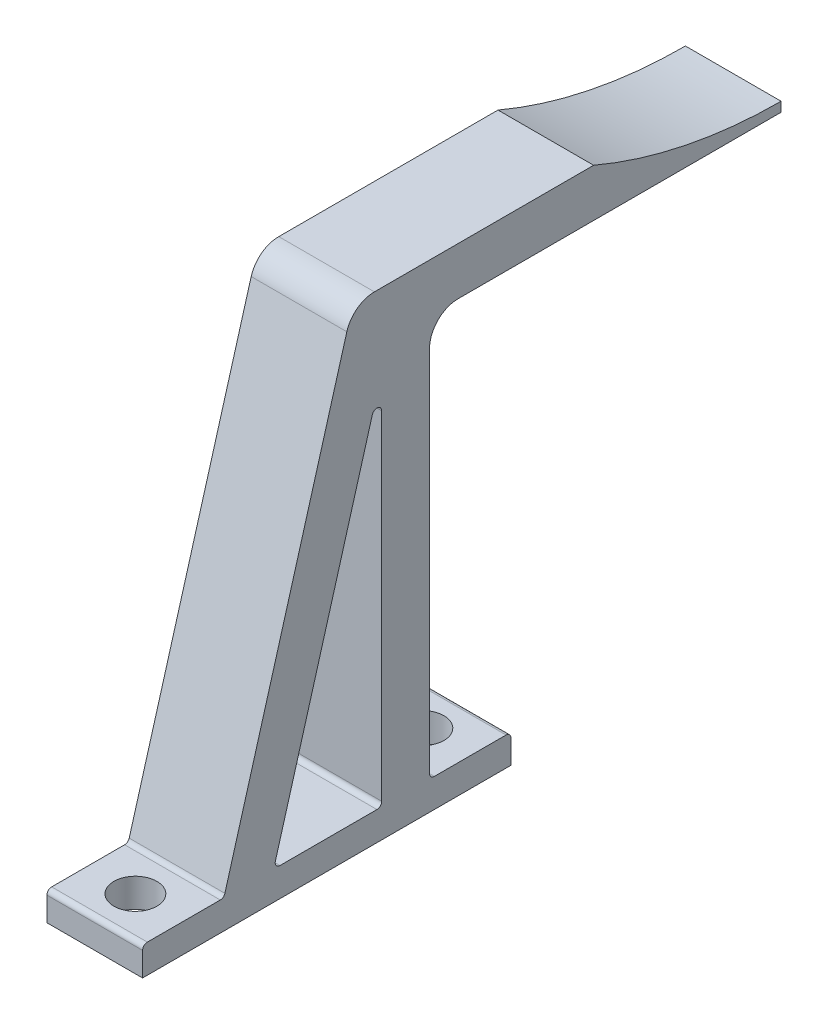
SolidWorks part; units mm, degrees
ref_plane "Front Plane" through (0, 0, 0) normal (0, 0, 1) x (1, 0, 0)
ref_plane "Top Plane" through (0, 0, 0) normal (0, 1, 0) x (1, 0, 0)
ref_plane "Right Plane" through (0, 0, 0) normal (1, 0, 0) x (0, 0, -1)
sketch "Sketch1" plane through (0, 0, 0) normal (1, 0, 0) x (0, 0, -1)
  line L0 (7.9802, 33.6971) -> (-4.7699, -10.7677)
  line L1 (-13.3737, -14.1299) -> (25.1263, -14.1299)
  line L2 (25.1263, -14.1299) -> (25.1263, -11.6299)
  line L3 (24.6263, -11.1299) -> (17.1263, -11.1299)
  line L4 (16.6263, -10.6299) -> (16.6263, 27.8701)
  line L5 (53.3763, 31.8701) -> (53.3763, 30.8701)
  line L6 (10.864, 35.8701) -> (33.7804, 35.8701)
  line L7 (53.3763, 30.8701) -> (19.6263, 30.8701)
  line L8 (-5.2505, -11.1299) -> (-12.8737, -11.1299)
  line L9 (-13.3737, -11.6299) -> (-13.3737, -14.1299)
  line L11 (0.9913, -11.1299) -> (11.1263, -11.1299)
  line L12 (11.6263, -10.6299) -> (11.6263, 24.715)
  line L13 (10.6457, 24.8528) -> (0.5107, -10.492)
  arc A0 (53.3763, 31.8701) -> (33.7804, 35.8701) centre (53.3763, 81.8701) cw
  arc A1 (0.9913, -11.1299) -> (0.5107, -10.492) centre (0.9913, -10.6299) cw
  arc A2 (19.6263, 30.8701) -> (16.6263, 27.8701) centre (19.6263, 27.8701) ccw
  arc A3 (11.6263, 24.715) -> (10.6457, 24.8528) centre (11.1263, 24.715) ccw
  arc A4 (7.9802, 33.6971) -> (10.864, 35.8701) centre (10.864, 32.8701) cw
  arc A5 (-4.7699, -10.7677) -> (-5.2505, -11.1299) centre (-5.2505, -10.6299) cw
  arc A6 (17.1263, -11.1299) -> (16.6263, -10.6299) centre (17.1263, -10.6299) cw
  arc A7 (-12.8737, -11.1299) -> (-13.3737, -11.6299) centre (-12.8737, -11.6299) ccw
  arc A8 (25.1263, -11.6299) -> (24.6263, -11.1299) centre (24.6263, -11.6299) ccw
  arc A9 (11.1263, -11.1299) -> (11.6263, -10.6299) centre (11.1263, -10.6299) ccw
  point P6 (0, 0)
  point P11 (0, 0)
  point P13 (16.4038, 32.062)
  point P14 (0, 0)
  point P22 (0, 0)
  point P26 (-4.8737, -11.1299)
  point P29 (16.6263, -11.1299)
  point P37 (0, 0)
  point P38 (16.2515, 26.3399)
  point P39 (0, 0)
  point P40 (0, 0)
  point P41 (16.9169, 31.2635)
  point P42 (0, 0)
  point P43 (11.1263, 31.1305)
  point P44 (0, 0)
  dimension "D1" = 50
  dimension "D12" = 0.5
  dimension "D14" = 3
  dimension "D16" = 0.5
  dimension "D17" = 0.5
  dimension "D18" = 0.5
  dimension "D19" = 0.5
  dimension "D22" = 0.5
  dimension "D23" = 0.5
  dimension "D5" = 3
  dimension "D2" = 50
  dimension "D3" = 8.5
  dimension "D4" = 3
  dimension "D6" = 66.75
  dimension "D7" = 1
  dimension "D8" = 38.5
  dimension "D9" = 8.5
  dimension "D10" = 5
  dimension "D11" = 66.75
  dimension "D15" = 106
  dimension "D20" = 5
  dimension "D21" = 5
extrude "Boss-Extrude1" add sketch "Sketch1" along normal blind 10 contours L0 A5 L8 A7 L9 L1 L2 A8 L3 A6 L4 A2 L7 L5 A0 L6 A4
extrude "Cut-Extrude2" cut sketch "Sketch1<5>" along normal blind 10 flip side to cut
sketch "Sketch1<5>" plane through (0, 0, 0) normal (1, 0, 0) x (0, 0, -1) same geometry as "Sketch1"
sketch "Sketch5" plane through (0, -14.1299, 0) normal (0, -1, 0) x (1, 0, 0)
  line L2 (5, 13.3737) -> (5, -25.1263) construction
  line L3 (10, 13.3737) -> (0, 13.3737) construction
  line L4 (10, -25.1263) -> (0, -25.1263) construction
  circle A0 centre (5, 9.1237) radius 2.25
  circle A1 centre (5, -20.8763) radius 2.25
  dimension "D1" = 4.5
  dimension "D2" = 4.5
  dimension "D3" = 4.25
  dimension "D4" = 4.25
extrude "Cut-Extrude3" cut sketch "Sketch5" against normal blind 10
